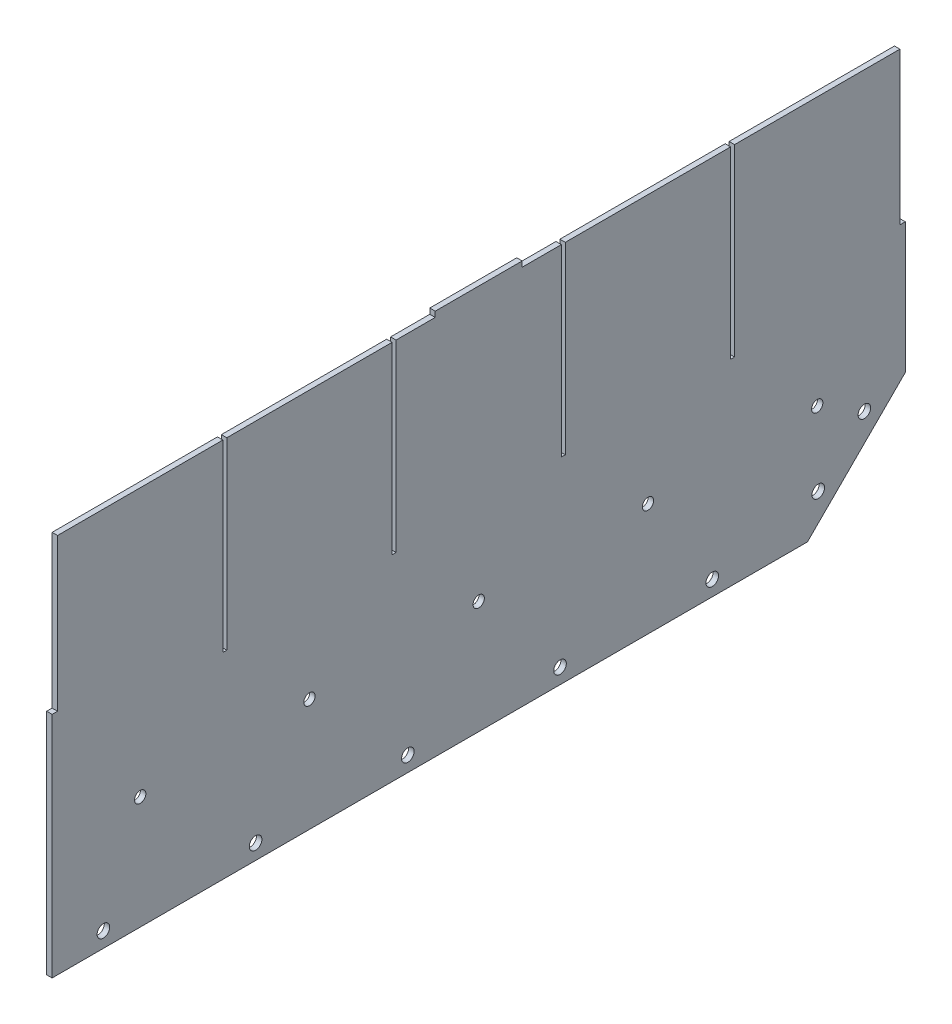
SolidWorks part; units mm, degrees
material "6061-T6 (SS)"
ref_plane "X-Y Datum" through (0, 0, 0) normal (0, 0, 1) x (1, 0, 0)
ref_plane "X-Z Datum" through (0, 0, 0) normal (0, 1, 0) x (1, 0, 0)
ref_plane "Y-Z Datum" through (0, 0, 0) normal (1, 0, 0) x (0, 0, -1)
sketch "Sketch1" plane through (0, 0, 0) normal (1, 0, 0) x (0, 0, -1)
  line L1 (-249.174, 82.55) -> (249.174, 82.55)
  line L2 (-249.174, 82.55) -> (-249.174, -82.55)
  line L3 (-249.174, -82.55) -> (249.174, -82.55)
  line L4 (249.174, 82.55) -> (249.174, -82.55)
  line L5 (-249.174, 82.55) -> (249.174, -82.55) construction
  line L6 (-249.174, -82.55) -> (249.174, 82.55) construction
  point P0 (0, 0)
  dimension "D1" = 165.1
  dimension "D2" = 498.348
extrude "Boss-Extrude1" add sketch "Sketch1" along normal mid plane 3.175
sketch "Sketch2" plane through (1.5875, 0, 0) normal (1, 0, 0) x (0, 0, -1)
  line L3 (192.024, -139.7) -> (-249.174, -139.7)
  line L5 (-249.174, -82.55) -> (249.174, -82.55) construction
  line L6 (-249.174, -82.55) -> (249.174, -82.55)
  line L7 (-249.174, -82.55) -> (-249.174, -139.7)
  line L12 (192.024, -139.7) -> (249.174, -82.55)
  line M10 (-249.174, -82.55) -> (249.174, -82.55)
  dimension "D1" = 45
  dimension "D5" = 57.15
extrude "Boss-Extrude2" add sketch "Sketch2" against normal blind 3.175 contours L3 L12 M10 region at (1.5875, -110.5456, 13.9978)
sketch "Sketch3" plane through (1.5875, 0, 0) normal (1, 0, 0) x (0, 0, -1)
  line L0 (-219.202, -139.7) -> (-219.202, -130.81)
  line L1 (192.024, -139.7) -> (-249.174, -139.7) construction
  line L2 (-219.202, -130.81) -> (-249.174, -130.81)
  line L3 (-249.174, 82.55) -> (-249.174, -139.7) construction
  circle A0 centre (-219.202, -130.81) radius 3.675
  dimension "D1" = 29.972
  dimension "D2" = 8.89
extrude "Cut-Extrude1" cut sketch "Sketch3" against normal blind 3.175 contours L2 A0 L0 | L0 A0 L2 region at (1.5875, -132.3697, 220.7617) region at (1.5875, -130.2901, 218.6821)
pattern_linear "LPattern1" count 5 spacing 88.9 along (0, 0, -1) of "Cut-Extrude1"
sketch "Sketch4" plane through (1.5875, 0, 0) normal (1, 0, 0) x (0, 0, -1)
  line L0 (192.024, -139.7) -> (183.9418, -131.6178)
  line L1 (183.9418, -131.6178) -> (198.3102, -117.2494)
  circle A0 centre (198.3102, -117.2494) radius 3.675
extrude "Cut-Extrude2" cut sketch "Sketch4" against normal through all contours A0 region at (1.5875, -120.5486, -199.6768)
pattern_linear "LPattern2" count 2 spacing 38.1 along (0, 0.7071, -0.7071) of "Cut-Extrude2"
sketch "Sketch5" plane through (-1.5875, 0, 0) normal (-1, 0, 0) x (0, 0, 1)
  line L1 (-249.174, 82.55) -> (-245.999, 82.55)
  line L2 (-249.174, 82.55) -> (-249.174, -6.35)
  line L3 (-249.174, -6.35) -> (-245.999, -6.35)
  line L4 (-245.999, 82.55) -> (-245.999, -6.35)
  line L5 (249.174, 82.55) -> (245.999, 82.55)
  line L6 (249.174, 82.55) -> (249.174, -6.35)
  line L7 (249.174, -6.35) -> (245.999, -6.35)
  line L8 (245.999, 82.55) -> (245.999, -6.35)
  dimension "D1" = 3.175
  dimension "D2" = 88.9
  dimension "D3" = 3.175
  dimension "D4" = 88.9
extrude "Cut-Extrude3" cut sketch "Sketch5" against normal through all
sketch "Sketch6" plane through (-1.5875, 0, 0) normal (-1, 0, 0) x (0, 0, 1)
  line L0 (-122.174, 82.55) -> (-249.174, 82.55) construction
  line L1 (-149.4282, 82.55) -> (-149.4282, -24.892) construction
  line L2 (-122.174, 82.55) -> (-249.174, 82.55)
  line L3 (-149.4282, 82.55) -> (-149.4282, -24.892)
  line L5 (-149.4282, 82.55) -> (-147.1422, 82.55)
  line L6 (-149.4282, 82.55) -> (-149.4282, -24.892)
  line L7 (-149.4282, -24.892) -> (-147.1422, -24.892)
  line L8 (-147.1422, 82.55) -> (-147.1422, -24.892)
  dimension "D1" = 2.286
  dimension "D2" = 107.442
extrude "Cut-Extrude4" cut sketch "Sketch6" against normal through all contours L8 L2 L3 L7 region at (-1.5875, 28.829, -148.2852)
pattern_linear "LPattern3" count 4 spacing 98.8568 along (0, 0, 1) of "Cut-Extrude4"
sketch "Sketch7" plane through (-1.5875, 0, 0) normal (-1, 0, 0) x (0, 0, 1)
  line L0 (122.174, 85.725) -> (25.4, 85.725) construction
  line L1 (25.4, 82.55) -> (-25.4, 82.55)
  line L2 (25.4, 82.55) -> (25.4, 85.725)
  line L3 (25.4, 85.725) -> (-25.4, 85.725)
  line L4 (-25.4, 82.55) -> (-25.4, 85.725)
  line L5 (25.4, 82.55) -> (-25.4, 85.725) construction
  line L6 (25.4, 85.725) -> (-25.4, 82.55) construction
  point P0 (0, 84.1375)
  dimension "D1" = 3.175
  dimension "D2" = 50.8
extrude "Boss-Extrude3" add sketch "Sketch7" against normal blind 3.175
sketch "Sketch8" plane through (1.5875, 0, 0) normal (1, 0, 0) x (0, 0, -1)
  line L0 (192.024, -139.7) -> (-249.174, -139.7) construction
  circle A0 centre (0, -73.8124) radius 3
  point P4 (0, 0)
  dimension "D1" = 6
  dimension "D2" = 65.8876
hole_wizard "M6 Clearance Hole1" positions "Sketch9" profile "Sketch10" hole size "M6" standard "ANSI Metric" end condition through all
sketch "Sketch9" plane through (1.5875, 0, 0) normal (1, 0, 0) x (0, 0, -1)
  point P0 (0, -73.8124)
sketch "Sketch10" plane through (1.5875, -73.8124, 0) normal (0, 1, 0) x (0, 0, -1)
  line L0 (0, 0) -> (0, 3.175)
  line L1 (0, 3.175) -> (3.3, 3.175)
  line L2 (3.3, 3.175) -> (3.3, 0)
  line L5 (3.3, 0) -> (0, 0)
  line L11 (0, -6.35) -> (0, 107.95) construction
  dimension "Thru Hole Dia." = 6.6
  dimension "Thru Hole Depth" = 3.175
pattern_linear "LPattern4" count 3 spacing 98.8568 along (0, 0, 1) count 3 spacing 98.8568 along (0, 0, -1) of "M6 Clearance Hole1"
